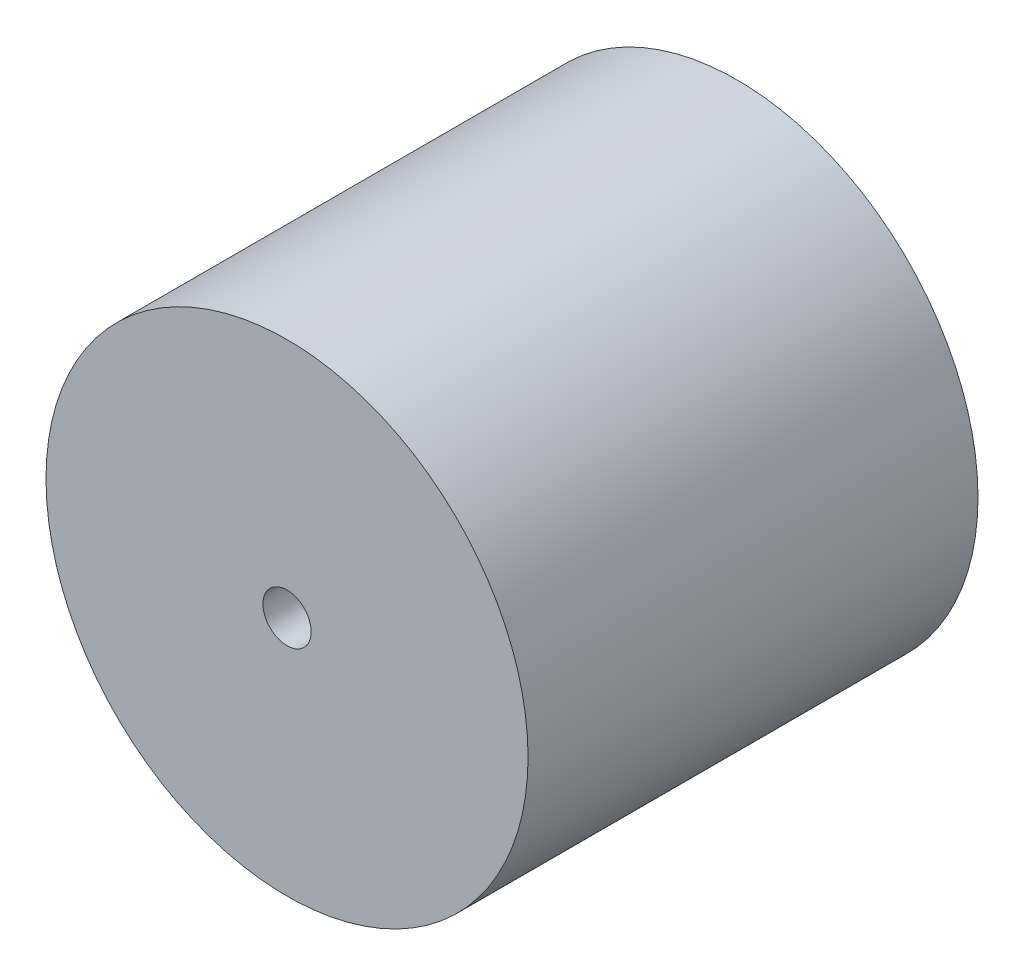
SolidWorks part; units mm, degrees
ref_plane "前视基准面" through (0, 0, 0) normal (0, 0, 1) x (1, 0, 0)
ref_plane "上视基准面" through (0, 0, 0) normal (0, 1, 0) x (1, 0, 0)
ref_plane "右视基准面" through (0, 0, 0) normal (1, 0, 0) x (0, 0, -1)
other "Configuration Table"
sketch "草图1" plane through (0, 0, 0) normal (0, 0, 1) x (1, 0, 0)
  circle A0 centre (0, 0) radius 15
extrude "凸台-拉伸2" add sketch "草图1" along normal blind 28
sketch "草图3" plane through (0, 0, 28) normal (0, 0, 1) x (1, 0, 0)
  circle A0 centre (0, 0) radius 1.5
extrude "切除-拉伸3" cut sketch "草图3" against normal blind 10
extrude "切除-拉伸4" cut sketch "草图3<2>" along normal blind 10 from surface starting at face at (15, 0, 0)
sketch "草图3<2>" plane through (0, 0, 28) normal (0, 0, 1) x (1, 0, 0) same geometry as "草图3"
